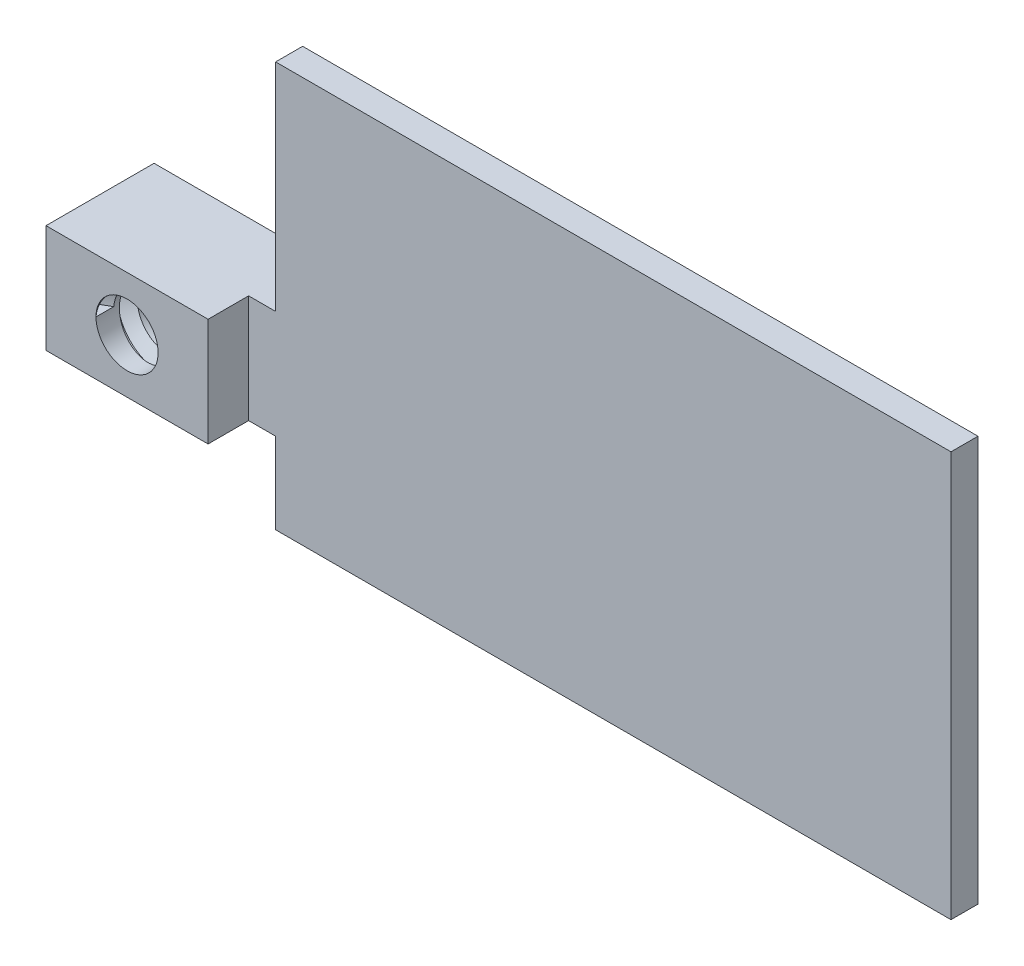
SolidWorks part; units mm, degrees
ref_plane "Front Plane" through (0, 0, 0) normal (0, 0, 1) x (1, 0, 0)
ref_plane "Top Plane" through (0, 0, 0) normal (0, 1, 0) x (1, 0, 0)
ref_plane "Right Plane" through (0, 0, 0) normal (1, 0, 0) x (0, 0, -1)
sketch "Sketch1" plane through (0, 0, 0) normal (0, 0, 1) x (1, 0, 0)
  line L0 (-25, -15) -> (-25, -9)
  line L5 (-25, 15) -> (25, 15)
  line L7 (-25, -15) -> (25, -15)
  line L8 (25, 15) -> (25, -15)
  line L9 (-25, -9) -> (-39, -9)
  line L10 (-39, -9) -> (-39, -1)
  line L11 (-39, -1) -> (-25, -1)
  line L12 (-25, -1) -> (-25, 15)
  point P4 (0, -15)
  point P5 (25, 0)
  dimension "D1" = 50
  dimension "D2" = 30
  dimension "D3" = 6
  dimension "D4" = 14
  dimension "D5" = 8
  dimension "D6" = 50
extrude "Boss-Extrude1" add sketch "Sketch1" along normal blind 2
sketch "Sketch2" plane through (0, 0, 2) normal (0, 0, 1) x (1, 0, 0)
  line L0 (-39, -9) -> (-25, -9) construction
  line L1 (-39, -1) -> (-27, -1)
  line L2 (-39, -1) -> (-39, -9)
  line L3 (-39, -9) -> (-27, -9)
  line L4 (-27, -1) -> (-27, -9)
  dimension "D1" = 12
extrude "Boss-Extrude2" add sketch "Sketch2" along normal blind 3 and the other way blind 5
sketch "Sketch3" plane through (0, 0, 5) normal (0, 0, 1) x (1, 0, 0)
  line L0 (-39, -1) -> (-39, -9) construction
  line L1 (-27, -1) -> (-39, -1) construction
  circle A0 centre (-33, -5) radius 2.3
  dimension "D1" = 6
  dimension "D2" = 4
extrude "Cut-Extrude1" cut sketch "Sketch3" against normal through all
thread "Thread1" pitch 1.75 method cut profile "Thread Profile4" start angle 0, offset 0, length 0, pitch 1.75, diameter 4.6
ref_plane "Plane4" through (-35.3, -5, 5) normal (0, -1, 0) x (-1, 0, 0)
sketch "Thread Profile4" plane through (-35.3, -5, 5) normal (0, -1, 0) x (-1, 0, 0)
  line L0 (0, 0) -> (0, 1.75) construction
  line L1 (0, 0) -> (0.9472, 0.5469)
  line L2 (0.9472, 0.5469) -> (0.9472, 0.7656)
  line L3 (0.9472, 0.7656) -> (0, 1.3125)
  line L4 (0.9472, 0.6562) -> (0, 0.6562) construction
  line L11 (0, 0) -> (0, 1.3125)
  point P2 (0, 0)
  dimension "Pitch" = 1.75
  dimension "Profile_Angle" = 60
  dimension "Profile_Land" = 0.2188
  dimension "Profile_Height" = 0.9472
